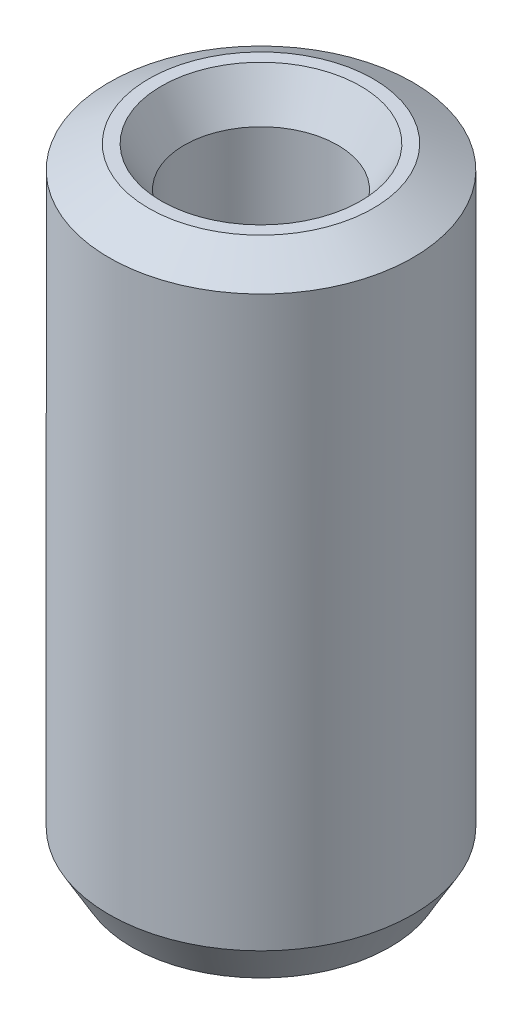
SolidWorks part; units mm, degrees
ref_plane "Front Plane" through (0, 0, 0) normal (0, 0, 1) x (1, 0, 0)
ref_plane "Top Plane" through (0, 0, 0) normal (0, 1, 0) x (1, 0, 0)
ref_plane "Right Plane" through (0, 0, 0) normal (1, 0, 0) x (0, 0, -1)
sketch "Sketch1" plane through (0, 0, 0) normal (0, 1, 0) x (1, 0, 0)
  circle A0 centre (0, 0) radius 15
  dimension "SLEEVE_OD" = 30
extrude "Boss-Extrude1" add sketch "Sketch1" along normal blind 62.3519
sketch "Sketch2" plane through (0, 0, 0) normal (0, 1, 0) x (1, 0, 0)
  circle A0 centre (0, 0) radius 7.5775
  dimension "BORE_D" = 15.155
extrude "Cut-Extrude1" cut sketch "Sketch2" along normal through all
chamfer "Chamfer1" distance 2.2623 angle 60 4 edges at (0, 62.3519, 7.5775) (0, 0, 7.5775) (0, 0, 15) (0, 62.3519, 15) first distance on face at (0, 62.3519, 7.5775) first distance on face at (0, 0, 7.5775) first distance on face at (0, 62.3519, 15)
